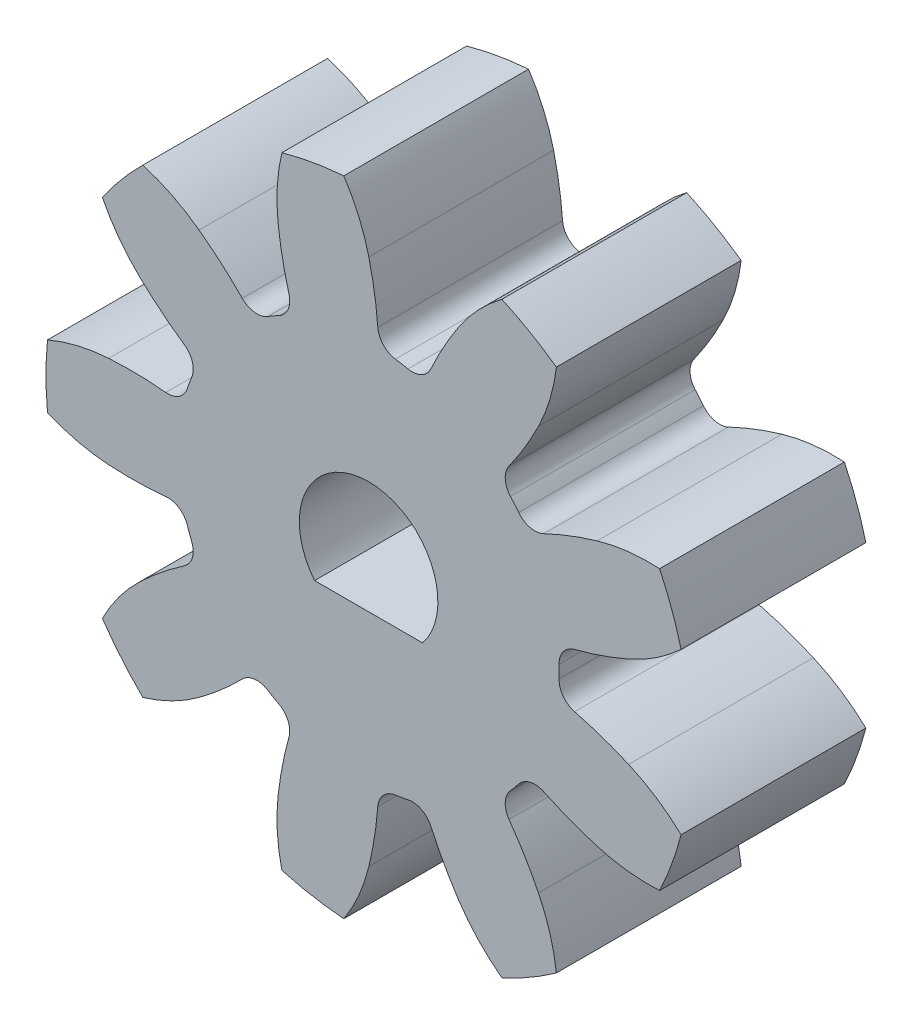
SolidWorks part; units mm, degrees
material "Plain Carbon Steel"
ref_plane "Front" through (0, 0, 0) normal (0, 0, 1) x (1, 0, 0)
ref_plane "Top" through (0, 0, 0) normal (0, 1, 0) x (1, 0, 0)
ref_plane "Right" through (0, 0, 0) normal (1, 0, 0) x (0, 0, -1)
sketch "Sketch1" plane through (0, 0, 0) normal (0, 0, 1) x (1, 0, 0)
  line L0 (0, 0) -> (5.715, 0) construction
  line L1 (5.715, 0) -> (6.985, 0) construction
  circle A0 centre (0, 0) radius 5.715 construction
  circle A1 centre (0, 0) radius 6.985
  dimension "pitch_diameter" = 11.43
  dimension "addendum" = 1.27
extrude "BLANK DISK" add sketch "Sketch1" along normal mid plane 4
sketch "Sketch2" plane through (0, 0, 2) normal (0, 0, 1) x (1, 0, 0)
  line L0 (0, 0) -> (4.1275, 0) construction
  line L1 (4.1275, 0) -> (5.715, 0) construction
  line L2 (0, 0) -> (-6.985, 0) construction
  line L3 (0, 0) -> (-5.3508, -4.4899) construction
  line L4 (-5.763, -3.9469) -> (-4.952, -2.8529) construction
  line L5 (-4.952, -2.8529) -> (-3.6958, -1.8377) construction
  line L6 (-6.9517, -0.6809) -> (-5.6273, -0.9976) construction
  line L7 (-5.6273, -0.9976) -> (-4.0124, -0.9679) construction
  line L8 (-4.3107, -3.6171) -> (-4.952, -2.8529) construction
  line L9 (-5.6273, -0.9976) -> (-5.6273, 0) construction
  line L12 (0, 0) -> (-5.6273, -0.9976) construction
  line L13 (0, 0) -> (-4.952, -2.8529) construction
  line L14 (-4.952, -2.8529) -> (-2.9471, -6.3328) construction
  line L15 (-5.6273, -0.9976) -> (-6.3283, 2.9568) construction
  line L16 (-4.952, -2.8529) -> (-5.6273, -0.9976) construction
  line L17 (-3.8786, -1.4117) -> (-4.0124, -0.9679) construction
  line L18 (-3.8786, -1.4117) -> (-3.6958, -1.8377) construction
  circle A0 centre (0, 0) radius 5.715 construction
  circle A1 centre (0, 0) radius 4.1275 construction
  circle A2 centre (0, 0) radius 6.985 construction
  arc A3 (-5.763, -3.9469) -> (-6.9517, -0.6809) centre (0, 0) cw
  arc A4 (-3.6958, -1.8377) -> (-4.0124, -0.9679) centre (0, 0) cw construction
  arc A6 (-5.763, -3.9469) -> (-4.952, -2.8529) centre (-2.199, -5.7416) cw
  arc A7 (-6.9517, -0.6809) -> (-5.6273, -0.9976) centre (-5.3752, 2.9848) ccw
  arc A8 (-4.952, -2.8529) -> (-3.9902, -2.0738) centre (0.3598, -8.4265) cw
  arc A9 (-5.6273, -0.9976) -> (-4.3897, -0.9762) centre (-5.1408, 6.6864) ccw
  arc A10 (-3.9902, -2.0738) -> (-3.829, -1.5411) centre (-4.2414, -1.707) ccw
  arc A11 (-4.3897, -0.9762) -> (-3.9238, -1.2807) centre (-4.3463, -1.4186) cw
  arc A12 (-3.829, -1.5411) -> (-3.9238, -1.2807) centre (0, 0) cw
  dimension "D12" = 3.9903
  dimension "D3" = 40
  dimension "D4" = 0.9976
  dimension "D5" = 0.9976
  dimension "D11" = 1.9744
  dimension "D14" = 9
  dimension "D15" = 9
  dimension "base_fillet" = 0.4445
  dimension "pitch_diameter" = 11.43
  dimension "deddendum" = 1.5875
extrude "GEAR TOOTH CUT" cut sketch "Sketch2" against normal through all
ref_axis "CENTER AXIS" through (0, 0, 50) along (0, 0, -1)
pattern_circular "GEAR TEETH REVOLVE" count 9 over 360 about axis through (0, 0, 50) along (0, 0, -1) of "GEAR TOOTH CUT"
sketch "Sketch4" plane through (0, 0, 2) normal (0, 0, 1) x (1, 0, 0)
  circle A0 centre (0, 0) radius 0.75
  dimension "D1" = 1.5
extrude "Hub Extrude" add sketch "Sketch4" along normal blind 0.635
sketch "Sketch3" plane through (0, 0, 2) normal (0, 0, 1) x (1, 0, 0)
  line L0 (-1.1689, -0.94) -> (1.1689, -0.94)
  arc A0 (1.1689, -0.94) -> (-1.1689, -0.94) centre (0, 0) ccw
  dimension "D1" = 3
  dimension "D2" = 0.94
extrude "HEX BORE CUT" cut sketch "Sketch3" against normal through all and the other way through all
equation "\"N_teeth\"= 9.000000"
equation "\"pitch_diameter\"= .45000000"
equation "\"Pd\"=\"N_teeth\"/\"pitch_diameter\""
equation "\"addendum\"=1.000/\"Pd\""
equation "\"face_width\"= 4mm"
equation "\"deddendum\"=1.250/\"Pd\""
equation "\"D3@Sketch2\" = 360/\"N_teeth\""
equation "\"tooth_thickness\"=1.571/\"Pd\""
equation "\"D4@Sketch2\" = \"tooth_thickness\"/2"
equation "\"D5@Sketch2\" = \"tooth_thickness\"/2"
equation "\"Pressure_Angle\"=14.500000"
equation "\"base_fillet\"=0.35/\"Pd\""
equation "\"D12@Sketch2\" = 2*\"tooth_thickness\""
equation "\"hub_diameter\"= 1.5mm"
equation "\"bore\"= 0.125000"
equation "\"hub_projection\"=0.250000"
equation "\"sss_diam\"=0.062500"
